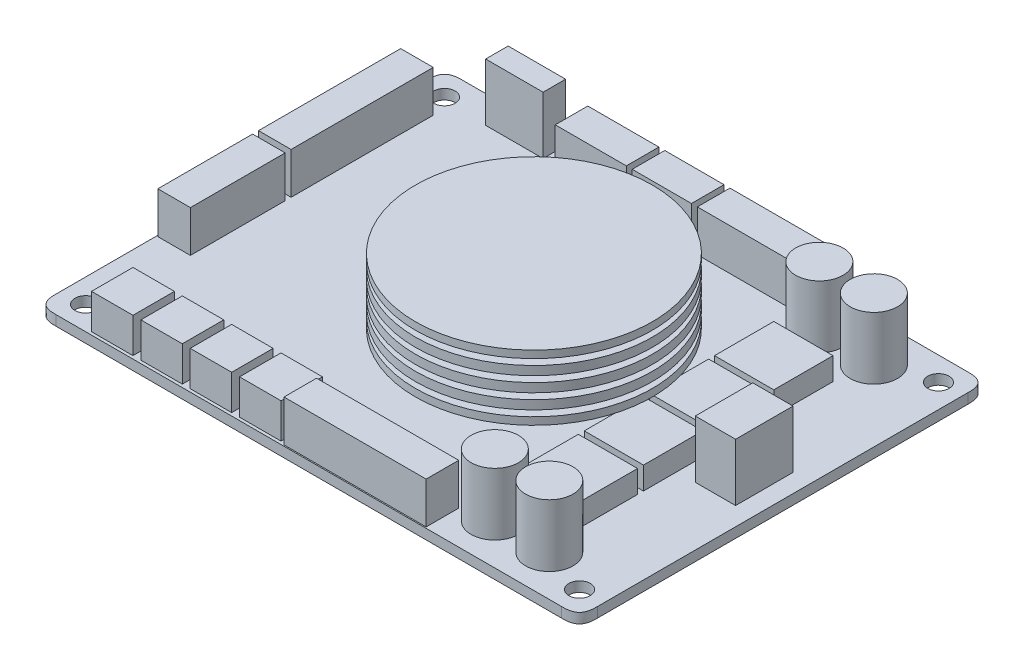
SolidWorks part; units mm, degrees
ref_plane "Front Plane" through (0, 0, 0) normal (0, 0, 1) x (1, 0, 0)
ref_plane "Top Plane" through (0, 0, 0) normal (0, 1, 0) x (1, 0, 0)
ref_plane "Right Plane" through (0, 0, 0) normal (1, 0, 0) x (0, 0, -1)
sketch "Sketch1" plane through (0, 0, 0) normal (0, 1, 0) x (1, 0, 0)
  line L1 (45.7, -34.3) -> (-45.7, -34.3)
  line L2 (45.7, -34.3) -> (45.7, 34.3)
  line L3 (45.7, 34.3) -> (-45.7, 34.3)
  line L4 (-45.7, -34.3) -> (-45.7, 34.3)
  line L5 (45.7, -34.3) -> (-45.7, 34.3) construction
  line L6 (45.7, 34.3) -> (-45.7, -34.3) construction
  point P0 (0, 0)
  dimension "D1" = 91.4
  dimension "D2" = 68.6
extrude "Boss-Extrude1" add sketch "Sketch1" along normal blind 1.7
sketch "Sketch2" plane through (0, 1.7, 0) normal (0, 1, 0) x (1, 0, 0)
  line L0 (45.7, -34.3) -> (45.7, 34.3) construction
  circle A0 centre (3.7, 0) radius 20
  dimension "D1" = 40
  dimension "D2" = 42
extrude "Boss-Extrude2" add sketch "Sketch2" along normal offset from surface (11 mm away) 15 from offset 4 up to face at (0, 1.7, 0) offset beyond the face yes
sketch "Sketch3" plane through (0, 1.7, 0) normal (0, 1, 0) x (1, 0, 0)
  line L0 (24.5, 27.4) -> (24.5, -27.4) construction
  line L1 (45.7, -34.3) -> (45.7, 34.3) construction
  line L2 (45.7, 34.3) -> (-45.7, 34.3) construction
  line L3 (-45.7, -34.3) -> (45.7, -34.3) construction
  line L4 (24.5, -27.4) -> (33.7, -27.4) construction
  line L5 (33.7, -27.4) -> (33.7, 27.4) construction
  line L6 (33.7, 27.4) -> (24.5, 27.4) construction
  circle A2 centre (24.5, 27.4) radius 4
  circle A3 centre (33.7, 27.4) radius 4
  circle A5 centre (33.7, -27.4) radius 4
  circle A6 centre (24.5, -27.4) radius 4
  point P1 (37.7, 27.4)
  point P10 (13.2905, 42.5285)
  point P14 (24.5, 31.4)
  point P20 (33.7, -31.4)
  dimension "D1" = 8
  dimension "D2" = 2
  dimension "D6" = 2.9
  dimension "D3" = 9.2
  dimension "D4" = 8
  dimension "D5" = 2.9
extrude "Boss-Extrude3" add sketch "Sketch3" along normal blind 10.5
sketch "Sketch4" plane through (0, 1.7, 0) normal (0, 1, 0) x (1, 0, 0)
  line L0 (32.7, 10.5) -> (32.7, 0.5)
  line L1 (32.7, 21.5) -> (22.7, 21.5)
  line L2 (32.7, 21.5) -> (32.7, 11.5)
  line L3 (32.7, 11.5) -> (22.7, 11.5)
  line L4 (22.7, 21.5) -> (22.7, 11.5)
  line L5 (32.7, 10.5) -> (22.7, 10.5)
  line L6 (22.7, 10.5) -> (22.7, 0.5)
  line L7 (32.7, 0.5) -> (22.7, 0.5)
  line L8 (32.7, -0.5) -> (32.7, -10.5)
  line L9 (32.7, -0.5) -> (22.7, -0.5)
  line L10 (22.7, -0.5) -> (22.7, -10.5)
  line L11 (32.7, -10.5) -> (22.7, -10.5)
  line L12 (32.7, -11.5) -> (32.7, -21.5)
  line L13 (32.7, -11.5) -> (22.7, -11.5)
  line L14 (22.7, -11.5) -> (22.7, -21.5)
  line L15 (32.7, -21.5) -> (22.7, -21.5)
  line L16 (27.7, 21.5) -> (27.7, -21.5) construction
  line L17 (27.7, 0) -> (0, 0) construction
  line L18 (45.7, -34.3) -> (45.7, 34.3) construction
  dimension "D1" = 10
  dimension "D2" = 4
  dimension "D3" = 43
  dimension "D4" = 13
extrude "Boss-Extrude4" add sketch "Sketch4" along normal blind 3.8
sketch "Sketch6" plane through (0, 16.7, 0) normal (0, 1, 0) x (1, 0, 0)
  circle A0 centre (3.7, 0) radius 10
  dimension "D1" = 20
extrude "Boss-Extrude5" add sketch "Sketch6" against normal up to surface (15 mm away) up to face at (24.5, 1.7, 31.4)
sketch "Sketch7" plane through (0, 1.7, 0) normal (0, 1, 0) x (1, 0, 0)
  line L0 (35.8, 0) -> (0, 0) construction
  line L1 (35.8, 4.85) -> (42.6, 4.85)
  line L2 (35.8, 4.85) -> (35.8, -4.85)
  line L3 (35.8, -4.85) -> (42.6, -4.85)
  line L4 (42.6, 4.85) -> (42.6, -4.85)
  line L5 (45.7, -34.3) -> (45.7, 34.3) construction
  line L6 (45.7, 34.3) -> (-45.7, 34.3) construction
  line L7 (-34.1, 33.45) -> (-24.4, 33.45)
  line L8 (-34.1, 33.45) -> (-34.1, 29.65)
  line L9 (-34.1, 29.65) -> (-24.4, 29.65)
  line L10 (-24.4, 33.45) -> (-24.4, 29.65)
  line L11 (-45.7, 34.3) -> (-45.7, -34.3) construction
  point P13 (-29.25, 29.65)
  dimension "D1" = 9.7
  dimension "D2" = 6.8
  dimension "D3" = 3.1
  dimension "D4" = 3.8
  dimension "D5" = 9.7
  dimension "D6" = 0.85
  dimension "D7" = 11.6
extrude "Boss-Extrude6" add sketch "Sketch7" along normal blind 9.7
sketch "Sketch8" plane through (0, 1.7, 0) normal (0, 1, 0) x (1, 0, 0)
  line L0 (-45.7, -34.3) -> (45.7, -34.3) construction
  line L1 (-4.4, -28.6) -> (19.6, -28.6)
  line L2 (-4.4, -28.6) -> (-4.4, -34.1)
  line L3 (-4.4, -34.1) -> (19.6, -34.1)
  line L4 (19.6, -28.6) -> (19.6, -34.1)
  line L14 (-40, 2.7) -> (-45.5, 2.7)
  line L15 (-45.7, 34.3) -> (-45.7, -34.3) construction
  line L16 (45.7, 34.3) -> (-45.7, 34.3) construction
  line L17 (-45.5, 1.7) -> (-40, 1.7)
  line L18 (-45.5, 1.7) -> (-45.5, -14.3)
  line L19 (-45.5, -14.3) -> (-40, -14.3)
  line L20 (-40, 1.7) -> (-40, -14.3)
  line L21 (-21.3, 34.1) -> (-9.3, 34.1)
  line L22 (-21.3, 34.1) -> (-21.3, 28.6)
  line L23 (-21.3, 28.6) -> (-9.3, 28.6)
  line L24 (-9.3, 34.1) -> (-9.3, 28.6)
  line L25 (-8.3, 34.1) -> (1.7, 34.1)
  line L26 (-8.3, 34.1) -> (-8.3, 28.6)
  line L27 (-8.3, 28.6) -> (1.7, 28.6)
  line L28 (1.7, 34.1) -> (1.7, 28.6)
  line L29 (2.7, 34.1) -> (18.7, 34.1)
  line L30 (2.7, 34.1) -> (2.7, 28.6)
  line L31 (2.7, 28.6) -> (18.7, 28.6)
  line L32 (18.7, 34.1) -> (18.7, 28.6)
  line L33 (45.7, -34.3) -> (45.7, 34.3) construction
  line L34 (-40, 2.7) -> (-40, 26.7)
  line L35 (-40, 26.7) -> (-45.5, 26.7)
  line L36 (-45.5, 2.7) -> (-45.5, 26.7)
  dimension "D1" = 0.2
  dimension "D2" = 24
  dimension "D3" = 26.1
  dimension "D4" = 5.5
  dimension "D5" = 5.5
  dimension "D8" = 20
  dimension "D9" = 16
  dimension "D10" = 0.2
  dimension "D11" = 1
  dimension "D12" = 1
  dimension "D13" = 16
  dimension "D14" = 10
  dimension "D15" = 12
  dimension "D16" = 0.2
  dimension "D17" = 27
  dimension "D18" = 1
  dimension "D19" = 24
extrude "Boss-Extrude7" add sketch "Sketch8" along normal blind 7
sketch "Sketch9" plane through (0, 1.7, 0) normal (0, 1, 0) x (1, 0, 0)
  line L0 (-45.7, -34.3) -> (45.7, -34.3) construction
  line L1 (-30.2, -33.8) -> (-37.2, -33.8)
  line L2 (-30.2, -33.8) -> (-30.2, -26.8)
  line L3 (-30.2, -26.8) -> (-37.2, -26.8)
  line L4 (-37.2, -33.8) -> (-37.2, -26.8)
  line L5 (-45.7, 34.3) -> (-45.7, -34.3) construction
  line L6 (-21.8667, -33.8) -> (-21.8667, -26.8)
  line L7 (-21.8667, -33.8) -> (-28.8667, -33.8)
  line L8 (-28.8667, -33.8) -> (-28.8667, -26.8)
  line L9 (-21.8667, -26.8) -> (-28.8667, -26.8)
  line L10 (-13.5333, -33.8) -> (-13.5333, -26.8)
  line L11 (-13.5333, -33.8) -> (-20.5333, -33.8)
  line L12 (-20.5333, -33.8) -> (-20.5333, -26.8)
  line L13 (-13.5333, -26.8) -> (-20.5333, -26.8)
  line L14 (-5.2, -33.8) -> (-5.2, -26.8)
  line L15 (-5.2, -33.8) -> (-12.2, -33.8)
  line L16 (-12.2, -33.8) -> (-12.2, -26.8)
  line L17 (-5.2, -26.8) -> (-12.2, -26.8)
  dimension "D1" = 7
  dimension "D2" = 0.5
  dimension "D3" = 8.5
  dimension "D5" = 32
  dimension "D4" = 4
extrude "Boss-Extrude8" add sketch "Sketch9" along normal blind 5.9
hole_wizard "M3 Clearance Hole1" positions "Sketch10" profile "Sketch11" hole size "M3" standard "ANSI Metric"
sketch "Sketch10" plane through (0, 1.7, 0) normal (0, 1, 0) x (1, 0, 0)
  line L1 (41.7, 30.3) -> (-41.7, 30.3)
  line L2 (41.7, 30.3) -> (41.7, -30.3)
  line L3 (41.7, -30.3) -> (-41.7, -30.3)
  line L4 (-41.7, 30.3) -> (-41.7, -30.3)
  line L8 (41.7, 30.3) -> (-41.7, -30.3)
  line L12 (-45.7, -34.3) -> (45.7, -34.3) construction
  line L13 (-45.7, 34.3) -> (-45.7, -34.3) construction
  point P1 (41.7, 30.3)
  point P2 (-41.7, -30.3)
  point P97 (41.7, -30.3)
  point P98 (-41.7, 30.3)
  dimension "D1" = 4
  dimension "D2" = 4
sketch "Sketch11" plane through (41.7, 1.7, -30.3) normal (1, 0, 0) x (0, 0, 1)
  line L0 (0, 0) -> (0, 8.5815)
  line L1 (0, 8.5815) -> (1.8, 7.5)
  line L2 (1.8, 7.5) -> (1.8, 0)
  line L5 (1.8, 0) -> (0, 0)
  line L10 (0, 8.5815) -> (-1.8, 7.5) construction
  line L11 (0, -6.35) -> (0, 107.95) construction
  dimension "Hole Dia." = 3.6
  dimension "Hole Depth" = 7.5
  dimension "Drill Angle" = 118
fillet "Fillet1" radius 3 4 edges at (-45.7, 0.85, 34.3) (-45.7, 0.85, -34.3) (45.7, 0.85, -34.3) (45.7, 0.85, 34.3) curvature continuous yes
sketch "Sketch12" plane through (0, 16.7, 0) normal (0, 1, 0) x (1, 0, 0)
  circle A0 centre (3.7, 0) radius 20
  circle A1 centre (3.7, 0) radius 20 construction
  circle A2 centre (3.7, 0) radius 18
  dimension "D1" = 2
extrude "Cut-Extrude1" cut sketch "Sketch12" against normal blind 1 from offset 1.25 offset against normal yes
pattern_linear "LPattern1" count 4 spacing 2.5 along (0, -1, 0) of "Cut-Extrude1"
